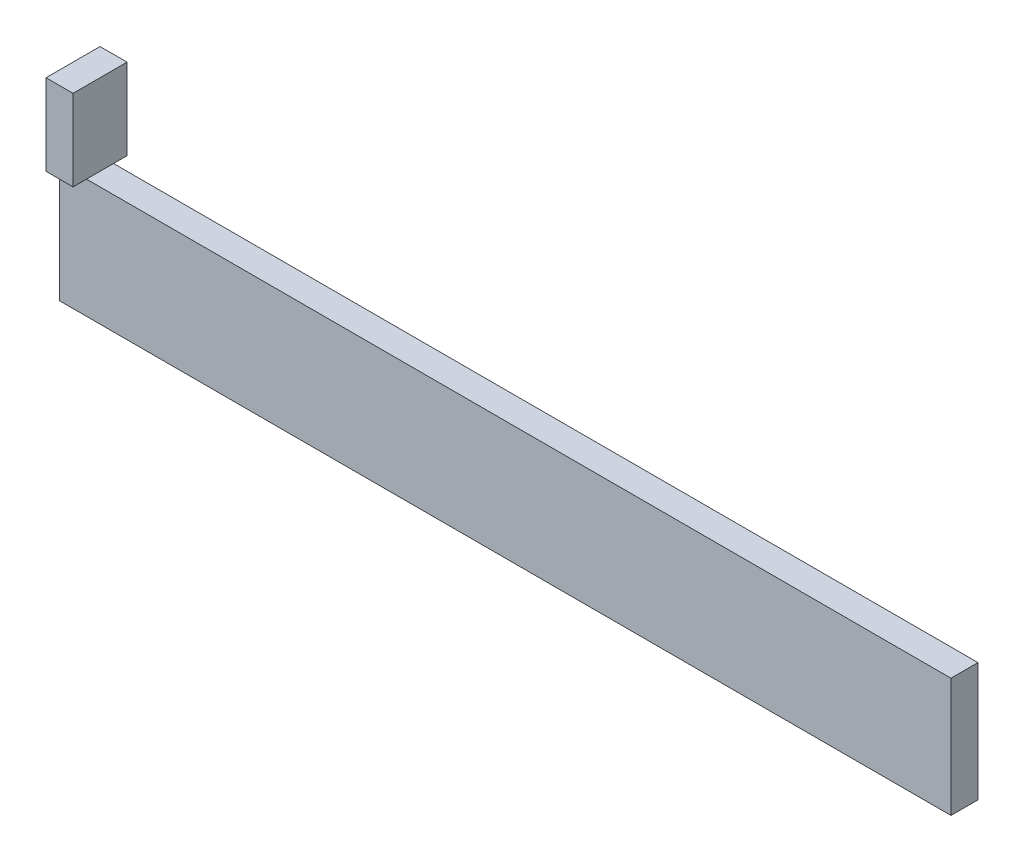
SolidWorks part; units mm, degrees
ref_plane "Front Plane" through (0, 0, 0) normal (0, 0, 1) x (1, 0, 0)
ref_plane "Top Plane" through (0, 0, 0) normal (0, 1, 0) x (1, 0, 0)
ref_plane "Right Plane" through (0, 0, 0) normal (1, 0, 0) x (0, 0, -1)
sketch "Sketch1" plane through (0, 0, 0) normal (0, 0, 1) x (1, 0, 0)
  line L1 (0, 0) -> (165, 0)
  line L2 (0, 0) -> (0, 22)
  line L3 (0, 22) -> (165, 22)
  line L4 (165, 0) -> (165, 22)
  dimension "D1" = 165
  dimension "D2" = 22
extrude "Boss-Extrude1" add sketch "Sketch1" along normal blind 5
sketch "Sketch2" plane through (0, 0, 0) normal (-1, 0, 0) x (0, 0, 1)
  line L1 (-2.5, 22) -> (7.5, 22)
  line L2 (-2.5, 22) -> (-2.5, 37)
  line L3 (-2.5, 37) -> (7.5, 37)
  line L4 (7.5, 22) -> (7.5, 37)
  line L7 (0, 22) -> (0, 0) construction
  line L8 (5, 22) -> (0, 22) construction
  point P5 (0, 0)
  dimension "D1" = 15
  dimension "D2" = 10
  dimension "D3" = 2.5
extrude "Boss-Extrude2" add sketch "Sketch2" against normal blind 5
